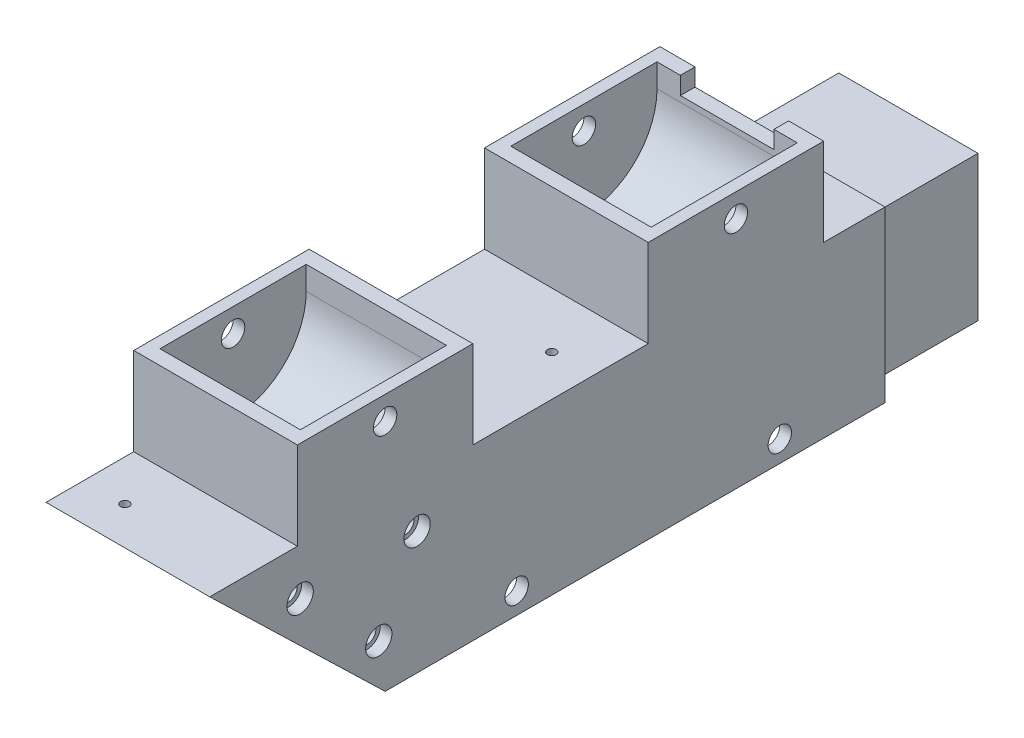
SolidWorks part; units mm, degrees
ref_plane "前视基准面" through (0, 0, 0) normal (0, 0, 1) x (1, 0, 0)
ref_plane "上视基准面" through (0, 0, 0) normal (0, 1, 0) x (1, 0, 0)
ref_plane "右视基准面" through (0, 0, 0) normal (1, 0, 0) x (0, 0, -1)
other "Configuration Table"
sketch "草图1" plane through (0, 0, 0) normal (1, 0, 0) x (0, 0, -1)
  line L0 (-150, 0) -> (150, 0) construction
  line L1 (-125, 14.5) -> (125, 14.5)
  line L2 (-125, 14.5) -> (-125, -14.5)
  line L3 (-125, -14.5) -> (125, -14.5)
  line L4 (125, 14.5) -> (125, -14.5)
  line L5 (-72.5, 29.5) -> (-72.5, 25.5)
  line L6 (-75, 14.5) -> (-45, 14.5)
  line L7 (-75, 14.5) -> (-75, 29.5)
  line L8 (-120, 10.8586) -> (120, 10.8586)
  line L9 (-120, 10.8586) -> (-120, -10.8586)
  line L10 (-120, -10.8586) -> (120, -10.8586)
  line L11 (120, 10.8586) -> (120, -10.8586)
  line L12 (-120, 10.8586) -> (120, -10.8586) construction
  line L13 (-120, -10.8586) -> (120, 10.8586) construction
  line L14 (-75, 29.5) -> (-45, 29.5)
  line L15 (-45, 14.5) -> (-45, 29.5)
  line L16 (-15, 14.5) -> (15, 14.5)
  line L17 (-15, 14.5) -> (-15, 29.5)
  line L18 (-15, 29.5) -> (15, 29.5)
  line L19 (15, 14.5) -> (15, 29.5)
  line L20 (45, 14.5) -> (75, 14.5)
  line L21 (45, 14.5) -> (45, 29.5)
  line L22 (45, 29.5) -> (75, 29.5)
  line L23 (75, 14.5) -> (75, 29.5)
  line L24 (-47.5, 29.5) -> (-47.5, 25.5)
  line L25 (-12.5, 29.5) -> (-12.5, 25.5)
  line L26 (12.5, 29.5) -> (12.5, 25.5)
  line L27 (47.5, 29.5) -> (47.5, 25.5)
  line L29 (72.5, 25.5) -> (72.5, 29.5)
  circle A2 centre (-67.5, -10.8586) radius 2
  circle A3 centre (-22.5, -10.8586) radius 2
  circle A4 centre (22.5, -10.8586) radius 2
  circle A5 centre (-60, 25.5) radius 2
  circle A6 centre (67.5, -10.8586) radius 2
  circle A7 centre (0, 25.5) radius 2
  circle A8 centre (60, 25.5) radius 2
  circle A9 centre (-60, 25.5) radius 12.5
  circle A10 centre (0, 25.5) radius 12.5
  circle A11 centre (60, 25.5) radius 12.5
  circle A12 centre (-67.5, -10.8586) radius 12.5
  circle A13 centre (-22.5, -10.8586) radius 12.5
  circle A14 centre (22.5, -10.8586) radius 12.5
  circle A15 centre (67.5, -10.8586) radius 12.5
  circle A16 centre (150, 0) radius 2
  circle A17 centre (-150, 0) radius 2
  circle A18 centre (-150, 0) radius 3.1
  point P10 (0, 0)
  point P12 (-125, 0)
  point P56 (-60, 29.5)
  point P62 (0, 29.5)
  point P64 (60, 29.5)
  dimension "D2" = 5
  dimension "D4" = 25
  dimension "D8" = 4
  dimension "D18" = 4
  dimension "D22" = 6.2
  dimension "D1" = 300
  dimension "D3" = 5
  dimension "D5" = 14.5
  dimension "D6" = 120
  dimension "D7" = 10.8586
  dimension "D9" = 52.5
  dimension "D10" = 45
  dimension "D11" = 45
  dimension "D12" = 45
  dimension "D13" = 60
  dimension "D14" = 60
  dimension "D15" = 60
  dimension "D16" = 60
  dimension "D17" = 52.5
  dimension "D19" = 30
  dimension "D20" = 4
  dimension "D21" = 15
extrude "凸台-拉伸1" add sketch "草图1" along normal blind 28 contours L1 L4 L3 L2 | L14 L15 L6 L7 | L18 L19 L16 L17 | L22 L23 L20 L21
extrude "切除-拉伸1" cut sketch "草图1<3>" along normal through all contours A2 | A3 | A4 | A6 | A8 | A7 | A5
sketch "草图1<3>" plane through (0, 0, 0) normal (1, 0, 0) x (0, 0, -1) same geometry as "草图1"
extrude "切除-拉伸2" cut sketch "草图1<5>" along normal offset from surface (24 mm away) 2 from offset 2 contours A9 L14 L5 | A9 L24 L14 | A10 L18 L25 | A10 L26 L18 | A11 L22 L27 | A11 L29 L22 | A12 | A9 | A13 | A10 | A14 | A11 | A15 region at (0, 28.5053, 72.3037) region at (0, 28.5053, 47.6963) region at (0, 28.5053, 12.3037) region at (0, 28.5053, -12.3037) region at (0, 28.5053, -47.6963) region at (0, 28.5053, -72.3037) up to face at (28, -10.8586, 65.5)
sketch "草图1<5>" plane through (0, 0, 0) normal (1, 0, 0) x (0, 0, -1) same geometry as "草图1"
sketch "草图3" plane through (0, 0, 125) normal (0, 0, 1) x (1, 0, 0)
  line L0 (28, 14.5) -> (28, -14.5) construction
  line L1 (28, 9.5) -> (22, 9.5)
  line L2 (28, 9.5) -> (28, -9.5)
  line L3 (28, -9.5) -> (22, -9.5)
  line L4 (22, 9.5) -> (22, -9.5)
  line L5 (28, 14.5) -> (0, 14.5) construction
  line L6 (28, -14.5) -> (0, -14.5) construction
  line L7 (0, 14.5) -> (0, -14.5) construction
  line L8 (0, 9.5) -> (6, 9.5)
  line L9 (0, 9.5) -> (0, -9.5)
  line L10 (0, -9.5) -> (6, -9.5)
  line L11 (6, 9.5) -> (6, -9.5)
  dimension "D1" = 6
  dimension "D2" = 5
  dimension "D3" = 5
extrude "凸台-拉伸2" add sketch "草图3" along normal blind 35 contours L1 L4 L3 L2
extrude "凸台-拉伸3" add sketch "草图3<3>" along normal blind 35 contours L2 L3 L4 L1 | L9 L10 L11 L8
sketch "草图3<3>" plane through (0, 0, 125) normal (0, 0, 1) x (1, 0, 0) same geometry as "草图3"
extrude "切除-拉伸3" cut sketch "草图1<6>" along normal through all contours A17
sketch "草图1<6>" plane through (0, 0, 0) normal (1, 0, 0) x (0, 0, -1) same geometry as "草图1"
extrude "切除-拉伸7" cut sketch "草图1<8>" along normal up to next contours A18
sketch "草图1<8>" plane through (0, 0, 0) normal (1, 0, 0) x (0, 0, -1) same geometry as "草图1"
fillet "圆角1" radius 9.5 4 edges at (25, 9.5, 160) (25, -9.5, 160) (3, -9.5, 160) (3, 9.5, 160)
fillet "圆角2" radius 5 2 edges at (14, -14.5, 125) (14, 14.5, 125)
sketch "草图4" plane through (0, 0, -125) normal (0, 0, -1) x (-1, 0, 0)
  line L1 (-28, 14.5) -> (0, 14.5) construction
  circle A0 centre (-14, 0) radius 5.1
  point P7 (-14, 14.5)
  dimension "D1" = 10.2
extrude "切除-拉伸4" cut sketch "草图4" against normal blind 31.5
extrude "切除-拉伸5" cut sketch "草图4<2>" against normal offset from surface (21.5 mm away) 10 flip side to cut up to face at (8.9, 0, -93.5)
sketch "草图4<2>" plane through (0, 0, -125) normal (0, 0, -1) x (-1, 0, 0) same geometry as "草图4"
sketch "草图5" plane through (0, 0, -103.5) normal (0, 0, -1) x (-1, 0, 0)
  line L0 (-28, 14.5) -> (0, 14.5) construction
  line L1 (-25.9, -12.4) -> (-2.1, -12.4)
  line L2 (-25.9, -12.4) -> (-25.9, 12.4)
  line L3 (-25.9, 12.4) -> (-2.1, 12.4)
  line L4 (-2.1, -12.4) -> (-2.1, 12.4)
  line L5 (-25.9, -12.4) -> (-2.1, 12.4) construction
  line L6 (-25.9, 12.4) -> (-2.1, -12.4) construction
  line L7 (0, -14.5) -> (0, 14.5) construction
  circle A0 centre (-14, 0) radius 5.1 construction
  point P0 (-14, 0)
  dimension "D1" = 2.1
  dimension "D2" = 2.1
extrude "切除-拉伸6" cut sketch "草图5" against normal blind 18 flip side to cut contours L3 L4 L1 L2
sketch "草图6" plane through (0, 14.5, 0) normal (0, 1, 0) x (1, 0, 0)
  circle A0 centre (7, 23.5) radius 0.75
  circle A1 centre (21, 35.5) radius 0.75
  circle A2 centre (7, -23.5) radius 0.75
  circle A3 centre (21, -35.5) radius 0.75
  dimension "D1" = 1.5
extrude "切除-拉伸8" cut sketch "草图6" against normal blind 4 contours A2 | A3 | A0 | A1
sketch "草图7" plane through (0, 14.5, 0) normal (0, 1, 0) x (1, 0, 0)
  circle A0 centre (7, -89.5) radius 0.75
  circle A1 centre (21.2, -110.5) radius 0.75
  dimension "D1" = 1.5
extrude "切除-拉伸9" cut sketch "草图7" against normal blind 4 contours A0 | A1
sketch "草图8" plane through (0, 0, 0) normal (-1, 0, 0) x (0, 0, 1)
  circle A0 centre (47, 4) radius 0.75
  circle A1 centre (2.499, -1.5) radius 0.75
  dimension "D1" = 1.5
extrude "切除-拉伸10" cut sketch "草图8" against normal blind 4
sketch "草图9" plane through (28, 0, 0) normal (1, 0, 0) x (0, 0, -1)
  circle A0 centre (-107.5, -0.5) radius 0.75
  circle A1 centre (-92.5, -0.5) radius 0.75
  dimension "D1" = 1.5
extrude "切除-拉伸11" cut sketch "草图9" against normal blind 4 contours A0 | A1
sketch "草图10" plane through (0, 0, 0) normal (-1, 0, 0) x (0, 0, 1)
  line L0 (30, 14.5) -> (0, -14.5)
  line L1 (45, 14.5) -> (15, 14.5) construction
  line L2 (120, -14.5) -> (-85.5, -14.5) construction
  line L3 (30, 14.5) -> (30, 45.5421)
  line L4 (30, 45.5421) -> (207.4503, 45.5421)
  line L5 (207.4503, 45.5421) -> (207.4503, -65.6361)
  line L6 (207.4503, -65.6361) -> (0, -65.6361)
  line L7 (0, -65.6361) -> (0, -14.5)
sketch "草图11" plane through (0, 0, 0) normal (1, 0, 0) x (0, 0, -1)
  line L0 (-30, 14.5) -> (0, -14.5) construction
  line L1 (-45, 14.5) -> (-15, 14.5) construction
  line L2 (-120, -14.5) -> (85.5, -14.5) construction
  circle A0 centre (-14.5301, 6.5) radius 0.75
  circle A1 centre (-1.0818, -6.5) radius 0.75
  circle A2 centre (-14.5301, 6.5) radius 2.25
  circle A3 centre (-1.0818, -6.5) radius 2.25
  circle A4 centre (-14.5301, 6.5) radius 1.5
  circle A5 centre (-1.0818, -6.5) radius 1.5
  circle A6 centre (5.4699, 6.5) radius 0.75
  circle A7 centre (5.4699, 6.5) radius 2.25
  circle A8 centre (5.4699, 6.5) radius 1.5
  dimension "D3" = 1.5
  dimension "D4" = 3
  dimension "D5" = 4.5
  dimension "D1" = 5
  dimension "D2" = 5
  dimension "D6" = 8
  dimension "D7" = 8
  dimension "D8" = 20
extrude "切除-拉伸12" cut sketch "草图11" along normal through all contours A1 | A0 | A6
extrude "切除-拉伸13" cut sketch "草图10" against normal through all
sketch "草图13" plane through (0, 0, 0) normal (0, 0, 1) x (1, 0, 0)
  line L0 (28, 14.5) -> (0, 14.5) construction
  line L1 (3.9, 10.6) -> (24.1, 10.6)
  line L2 (3.9, 10.6) -> (3.9, -10.6)
  line L3 (3.9, -10.6) -> (24.1, -10.6)
  line L4 (24.1, 10.6) -> (24.1, -10.6)
  line L5 (28, -14.5) -> (0, -14.5) construction
  line L6 (28, 14.5) -> (28, -14.5) construction
  line L7 (0, 45.5421) -> (0, -65.6361) construction
  dimension "D1" = 3.9
  dimension "D2" = 3.9
  dimension "D3" = 3.9
  dimension "D4" = 3.9
extrude "切除-拉伸14" cut sketch "草图13" against normal blind 40 from vertex starting at point (0, 14.5, 30)
extrude "切除-拉伸18" cut sketch "草图11<5>" along normal through all contours A4 | A8 | A5
sketch "草图11<5>" plane through (0, 0, 0) normal (1, 0, 0) x (0, 0, -1) same geometry as "草图11"
extrude "切除-拉伸19" cut sketch "草图11<6>" along normal blind 2 contours A7 | A3 | A2
sketch "草图11<6>" plane through (0, 0, 0) normal (1, 0, 0) x (0, 0, -1) same geometry as "草图11"
extrude "切除-拉伸20" cut sketch "草图11<7>" against normal blind 2 from surface contours A2 | A7 | A3 starting at face at (28, 6.5, 13.0301)
sketch "草图11<7>" plane through (0, 0, 0) normal (1, 0, 0) x (0, 0, -1) same geometry as "草图11"
sketch "草图15" plane through (0, 29.5, 0) normal (0, 1, 0) x (1, 0, 0)
  line L0 (26, 72.5) -> (2, 72.5) construction
  line L1 (6, 75) -> (22, 75)
  line L2 (6, 75) -> (6, 70)
  line L3 (6, 70) -> (22, 70)
  line L4 (22, 75) -> (22, 70)
  line L5 (6, 75) -> (22, 70) construction
  line L6 (6, 70) -> (22, 75) construction
  line L7 (28, 75) -> (0, 75) construction
  line L8 (2, 47.5) -> (2, 72.5) construction
  line L9 (6, 70) -> (22, 70)
  line L10 (6, 70) -> (6, 60)
  line L11 (6, 60) -> (22, 60)
  line L12 (22, 70) -> (22, 60)
  point P0 (14, 72.5)
  point P7 (14, 72.5)
  point P14 (2, 60)
  line M12 (28, 75) -> (0, 75)
  line M15 (2, 72.5) -> (26, 72.5)
  dimension "D1" = 16
extrude "切除-拉伸21" cut sketch "草图15" against normal blind 3 contours L4 L2 M12 M15 | L4 L2 L3 M15 | L12 L3 L10 L11 region at (14, 29.5, -73.75) region at (14, 29.5, -71.25) region at (14, 29.5, -65)
ref_plane "基准面1" through (-10, 0, 0) normal (1, 0, 0) x (0, 0, -1)
sketch "草图14" plane through (-10, 0, 0) normal (1, 0, 0) x (0, 0, -1)
  line L1 (-150, 50) -> (150, 50)
  line L2 (-150, 50) -> (-150, -50)
  line L3 (-150, -50) -> (150, -50)
  line L4 (150, 50) -> (150, -50)
  point P4 (-150, 0)
  point P6 (0, -50)
  dimension "D1" = 300
  dimension "D2" = 100
